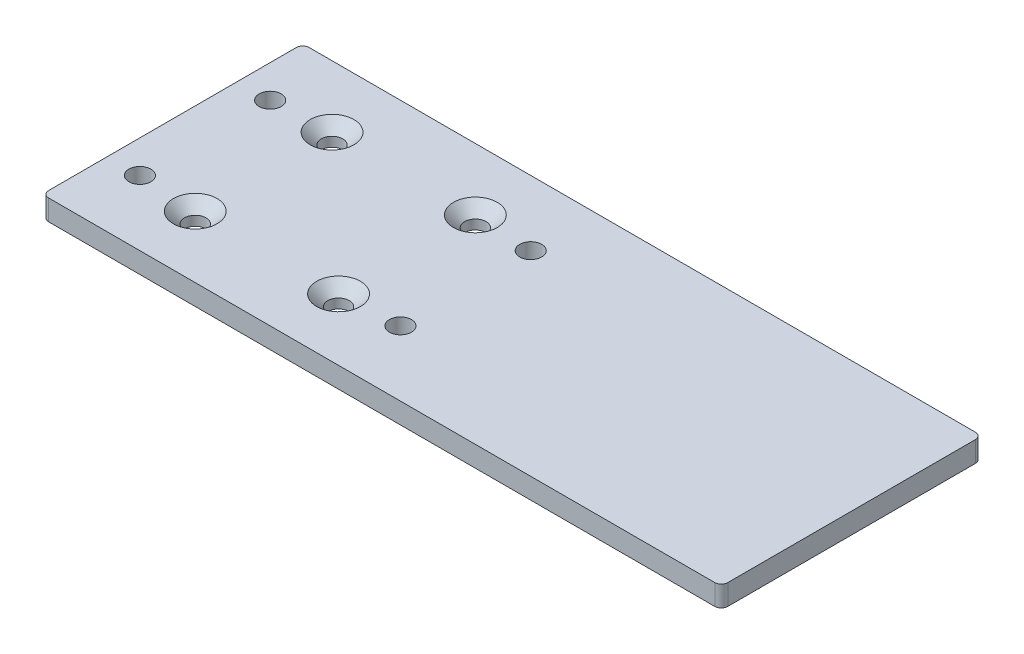
SolidWorks part; units mm, degrees
note: The reader was unsure of these and kept them because the rebuilt part matched: thickness of "Brida base1", "Chapa metálica1", "Chapa metálica2", "Chapa metálica3".
ref_plane "Alzado" through (0, 0, 0) normal (0, 0, 1) x (1, 0, 0)
ref_plane "Planta" through (0, 0, 0) normal (0, 1, 0) x (1, 0, 0)
ref_plane "Vista lateral" through (0, 0, 0) normal (1, 0, 0) x (0, 0, -1)
sketch "Croquis1" plane through (0, 0, 0) normal (0, 1, 0) x (1, 0, 0)
  line L1 (-149.7778, 34.4444) -> (58.7222, 34.4444)
  line L2 (-149.7778, 34.4444) -> (-149.7778, -45.5556)
  line L3 (-149.7778, -45.5556) -> (58.7222, -45.5556)
  line L4 (58.7222, 34.4444) -> (58.7222, -45.5556)
  dimension "120" = 208.5
  dimension "D2" = 80
base flange "Brida base1" sketch "Croquis1" thickness 6.35 reverse thickness direction no parameters "D1"=10
fillet "Redondeo1" radius 2 4 edges at (-149.7778, -3.175, -34.4444) (58.7222, -3.175, -34.4444) (58.7222, -3.175, 45.5556) (-149.7778, -3.175, 45.5556)
hole_wizard "Taladro de margen para 1/41" positions "Croquis7" profile "Croquis6" hole size "1/4" standard "Ansi Inch" end condition through all
sketch "Croquis7" plane through (0, 0, 0) normal (0, 1, 0) x (1, 0, 0)
  line L0 (-149.7778, 32.4444) -> (-149.7778, -43.5556) construction
  line L11 (-149.7778, -5.5556) -> (58.7222, -5.5556) construction
  line L12 (58.7222, -43.5556) -> (58.7222, 32.4444) construction
  point P2 (-139.7778, -25.5556)
  point P4 (-59.7778, -25.5556)
  point P66 (-139.7778, 14.4444)
  point P68 (-59.7778, 14.4444)
  dimension "D1" = 80
  dimension "D2" = 20
  dimension "D3" = 20
  dimension "15" = 10
sketch "Croquis6" plane through (-139.7778, 0, 25.5556) normal (1, 0, 0) x (0, 0, 1)
  line L0 (0, 0) -> (0, 6.35)
  line L1 (0, 6.35) -> (3.3782, 6.35)
  line L2 (3.3782, 6.35) -> (3.3782, 0)
  line L5 (3.3782, 0) -> (0, 0)
  line L11 (0, -6.35) -> (0, 107.95) construction
  dimension "Diámetro de taladro hasta el siguiente" = 6.7564
  dimension "Profundidad de taladro hasta el siguiente" = 6.35
sketch "Croquis8" plane through (0, 0, 0) normal (0, 1, 0) x (1, 0, 0)
  line L0 (-149.7778, -5.5556) -> (58.7222, -5.5556) construction
  line L1 (-149.7778, 32.4444) -> (-149.7778, -43.5556) construction
  line L2 (58.7222, -43.5556) -> (58.7222, 32.4444) construction
  line L3 (-45.5278, 34.4444) -> (-45.5278, -45.5556) construction
  line L4 (56.7222, 34.4444) -> (-147.7778, 34.4444) construction
  line L5 (-147.7778, -45.5556) -> (56.7222, -45.5556) construction
hole_wizard "Refrentado para tornillo tapón con cabeza plana de clavija de M61" positions "Croquis10" profile "Croquis9" countersink size "M6" standard "Ansi Metric" end condition through all
sketch "Croquis10" plane through (0, 0, 0) normal (0, 1, 0) x (1, 0, 0)
  line L1 (-149.7778, -5.5556) -> (58.7222, -5.5556) construction
  circle A0 centre (-139.7778, -25.5556) radius 3.3782 construction
  point P0 (-121.7778, 15.4444)
  point P2 (-77.7778, 15.4444)
  point P4 (-77.7778, -26.5556)
  point P6 (-121.7778, -26.5556)
  dimension "D3" = 18
  dimension "D1" = 42
  dimension "D2" = 44
  dimension "D4" = 21
sketch "Croquis9" plane through (-121.7778, 0, -15.4444) normal (1, 0, 0) x (0, 0, 1)
  line L0 (0, 0) -> (0, 6.35)
  line L1 (0, 6.35) -> (3.3, 6.35)
  line L2 (3.3, 6.35) -> (3.3, 3.42)
  line L3 (3.3, 3.42) -> (6.72, 0)
  line L5 (6.72, 0) -> (0, 0)
  line L6 (-3.3, 3.42) -> (-6.72, 0) construction
  line L11 (0, -6.35) -> (0, 107.95) construction
  dimension "Diámetro de taladro hasta el siguiente" = 6.6
  dimension "Profundidad de taladro hasta el siguiente" = 6.35
  dimension "Diámetro de avellanado cercano" = 13.44
  dimension "Ángulo de avellanado cercano" = 90
sketch "Líneas de pliegue1" [suppressed] plane through (0, 0, 0) normal (0, 1, 0) x (1, 0, 0)
sketch "Cuadro delimitador1" [suppressed] plane through (0, 0, 0) normal (0, 1, 0) x (1, 0, 0)
sheet metal parameters "Chapa metálica1" thickness 6.35 parameters "D1"=10, "D7"=3
flat pattern "Chapa desplegada1" [suppressed]
sketch "Líneas de pliegue2" plane through (0, 0, 0) normal (0, 1, 0) x (1, 0, 0)
sketch3d "Cuadro delimitador2" [suppressed]
  line L0 (-149.7778, -45.5554, 0) -> (110.2222, -45.5556, 0) construction
  line L1 (-149.7777, 34.4444, 0) -> (110.2223, 34.4443, 0) construction
  line L2 (-149.7778, -45.5554, 0) -> (-149.7777, 34.4444, 0) construction
  line L3 (110.2222, -45.5556, 0) -> (110.2223, 34.4443, 0) construction
sheet metal parameters "Chapa metálica2" thickness 6.35 parameters "D1"=10
flat pattern "Chapa desplegada1"
sketch "Líneas de pliegue2" plane through (0, 0, 0) normal (0, 1, 0) x (1, 0, 0)
sketch3d "Cuadro delimitador2" [suppressed]
  line L0 (-149.7778, -85.5554, 0) -> (110.2222, -85.5556, 0) construction
  line L1 (-149.7777, 34.4444, 0) -> (110.2223, 34.4443, 0) construction
  line L2 (-149.7778, -85.5554, 0) -> (-149.7777, 34.4444, 0) construction
  line L3 (110.2222, -85.5556, 0) -> (110.2223, 34.4443, 0) construction
sheet metal parameters "Chapa metálica3" thickness 6.35 parameters "D1"=10
flat pattern "Chapa desplegada1"
sketch "Líneas de pliegue2" plane through (0, 0, 0) normal (0, 1, 0) x (1, 0, 0)
sketch3d "Cuadro delimitador2" [suppressed]
  line L0 (-149.7778, -45.5554, 0) -> (58.7222, -45.5556, 0) construction
  line L1 (-149.7777, 34.4444, 0) -> (58.7223, 34.4443, 0) construction
  line L2 (-149.7778, -45.5554, 0) -> (-149.7777, 34.4444, 0) construction
  line L3 (58.7222, -45.5556, 0) -> (58.7223, 34.4443, 0) construction
